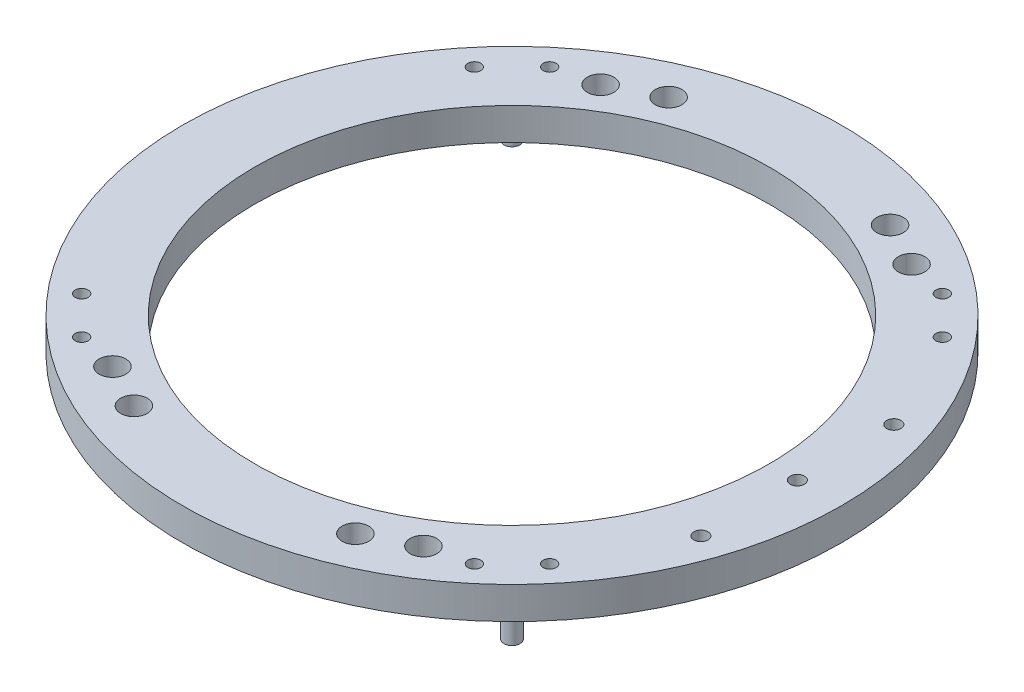
SolidWorks part; units mm, degrees
ref_plane "Front Plane" through (0, 0, 0) normal (0, 0, 1) x (1, 0, 0)
ref_plane "Top Plane" through (0, 0, 0) normal (0, 1, 0) x (1, 0, 0)
ref_plane "Right Plane" through (0, 0, 0) normal (1, 0, 0) x (0, 0, -1)
sketch "Sketch1" plane through (0, 0, 0) normal (0, 0, 1) x (1, 0, 0)
  line L0 (0, 1125.8152) -> (0, -48874.1848) construction
  line L1 (101.6, 1057.275) -> (114.3, 1057.275)
  line L3 (104.775, 955.675) -> (114.3, 955.675) construction
  line L4 (114.3, 1057.275) -> (114.3, 955.675) construction
  line L9 (101.6, 1069.975) -> (130.175, 1069.975)
  line L10 (101.6, 1069.975) -> (101.6, 1057.275)
  line L11 (101.6, 1057.275) -> (130.175, 1057.275)
  line L12 (130.175, 1069.975) -> (130.175, 1057.275)
  line L13 (104.775, 1057.275) -> (104.775, 955.675) construction
  line L14 (104.775, 1044.575) -> (104.775, 1057.275) construction
  line L15 (104.775, 968.375) -> (104.775, 955.675) construction
  line L16 (130.175, 955.675) -> (101.6, 955.675) construction
revolve "Revolve1" add sketch "Sketch1" angle 360 about L0 region at (115.8875, 1063.625, 0)
sketch "Sketch5" [suppressed] plane through (0, 1057.275, 0) normal (0, -1, 0) x (1, 0, 0)
  line L0 (0, 0) -> (107.3882, 47.625) construction
  line L1 (0, 0) -> (107.3882, -47.625) construction
  line L2 (0, 0) -> (117.475, 0) construction
  line L3 (107.3882, -47.625) -> (96.8765, -47.625)
  line L4 (107.3882, 47.625) -> (96.8765, 47.625)
  circle A0 centre (0, 0) radius 107.95 construction
  circle A1 centre (0, 0) radius 117.475
  arc A2 (107.3882, -47.625) -> (107.3882, 47.625) centre (0, 0) ccw
  circle A3 centre (0, 0) radius 107.95
  arc A4 (96.8765, -47.625) -> (96.8765, 47.625) centre (0, 0) ccw
  circle A5 centre (0, 0) radius 117.475 construction
  dimension "D3" = 95.25
  dimension "D1" = 0
  dimension "D2" = 0
extrude "Cut-Extrude1" [suppressed] cut sketch "Sketch5" along normal through all flip side to cut
sketch "Sketch11" [suppressed] plane through (0, 1057.275, 0) normal (0, -1, 0) x (1, 0, 0)
  line L0 (117.475, 47.625) -> (117.475, -47.625)
  line L1 (117.475, 47.625) -> (107.3882, 47.625)
  line L2 (107.3882, -47.625) -> (117.475, -47.625)
  arc A1 (107.3882, -47.625) -> (107.3882, 47.625) centre (0, 0) ccw construction
  arc A2 (107.3882, -47.625) -> (107.3882, 47.625) centre (0, 0) ccw
  point P3 (117.475, 0)
extrude "Boss-Extrude2" [suppressed] add sketch "Sketch11" along normal up to surface (101.6 mm away)
sketch "Sketch2" [suppressed] plane through (0, 0, 0) normal (0, 0, 1) x (1, 0, 0)
  line L0 (65.7096, 1044.575) -> (117.475, 1044.575)
  line L1 (117.475, 1044.575) -> (117.475, 1006.475)
  line L2 (184.3824, 1006.475) -> (0, 1006.475) construction
  line L3 (117.475, 1006.475) -> (65.7096, 1006.475)
  line L4 (65.7096, 1006.475) -> (65.7096, 1044.575)
  line L5 (184.3824, 1006.475) -> (0, 1006.475) construction
revolve "Cut-Revolve2" [suppressed] cut sketch "Sketch2" angle 360 about L5
sketch "Sketch6" plane through (0, 1057.275, 0) normal (0, -1, 0) x (1, 0, 0)
  line L0 (-85.3124, -85.3124) -> (85.3124, 85.3124) construction
  line L1 (-85.3124, 85.3124) -> (85.3124, -85.3124) construction
  line L2 (0, 0) -> (0, 120.65) construction
  circle A0 centre (0, 0) radius 120.65 construction
  circle A1 centre (-85.3124, 85.3124) radius 3.175
  circle A2 centre (85.3124, 85.3124) radius 3.175
  circle A3 centre (85.3124, -85.3124) radius 3.175
  circle A4 centre (-85.3124, -85.3124) radius 3.175
  point P5 (0, 0)
  point P8 (0, 0)
  dimension "D2" = 241.3
  dimension "D3" = 6.35
  dimension "D1" = 45
extrude "Boss-Extrude1" add sketch "Sketch6" along normal blind 12.7
hole_wizard "1/4-20 Tapped Hole1" positions "Sketch9" profile "Sketch10" tap size "1/4-20" standard "ANSI Inch" end condition through all
sketch "Sketch9" plane through (0, 1057.275, 0) normal (0, -1, 0) x (-1, 0, 0)
  line L0 (0, 0) -> (85.3124, 85.3124) construction
  line L3 (0, 0) -> (77.5523, 92.4233) construction
  arc A0 (77.5523, 92.4233) -> (92.4233, 77.5523) centre (0, 0) cw
  point P0 (77.5523, 92.4233)
  point P2 (92.4233, 77.5523)
  dimension "D1" = 5
sketch "Sketch10" plane through (-77.5523, 1057.275, -92.4233) normal (1, 0, 0) x (0, 0, -1)
  line L0 (0, 0) -> (0, 12.7)
  line L1 (0, 12.7) -> (2.5527, 12.7)
  line L2 (2.5527, 12.7) -> (2.5527, 0)
  line L5 (2.5527, 0) -> (0, 0)
  line L11 (0, -6.35) -> (0, 107.95) construction
  dimension "Thru Tap Drill Dia." = 5.1054
  dimension "Thru Tap Drill Depth" = 12.7
cosmetic thread "Hole Thread1" parameters "D2"=6.35
cosmetic thread "Hole Thread2" parameters "D2"=6.35
pattern_circular "CirPattern1" count 4 over 360 about axis through (0, 1125.8152, 0) along (0, 1, 0) of "1/4-20 Tapped Hole1"
ref_plane "Plane1" through (0, 1063.625, 0) normal (0, 1, 0) x (1, 0, 0)
sketch "Sketch12" plane through (0, 1063.625, 0) normal (0, 1, 0) x (1, 0, 0)
  line L0 (55.5625, -96.2371) -> (-55.5625, 96.2371) construction
  line L1 (55.5625, 96.2371) -> (-55.5625, -96.2371) construction
  line L2 (0, 0) -> (-111.125, 0) construction
  line L3 (-65.8243, -101.311) -> (-56.2993, -84.8132)
  line L4 (-65.8243, -101.311) -> (-54.8257, -107.661)
  line L5 (-56.2993, -84.8132) -> (-45.3007, -91.1632)
  line L6 (-54.8257, -107.661) -> (-45.3007, -91.1632)
  line L7 (-65.8243, -101.311) -> (-45.3007, -91.1632) construction
  line L8 (-56.2993, -84.8132) -> (-54.8257, -107.661) construction
  line L9 (-54.8257, 107.661) -> (-45.3007, 91.1632)
  line L10 (-54.8257, 107.661) -> (-65.8243, 101.311)
  line L11 (-45.3007, 91.1632) -> (-56.2993, 84.8132)
  line L12 (-65.8243, 101.311) -> (-56.2993, 84.8132)
  line L13 (-54.8257, 107.661) -> (-56.2993, 84.8132) construction
  line L14 (-45.3007, 91.1632) -> (-65.8243, 101.311) construction
  line L15 (0, 0) -> (0, 130.175) construction
  line L16 (45.3007, 91.1632) -> (65.8243, 101.311) construction
  line L17 (54.8257, 107.661) -> (56.2993, 84.8132) construction
  line L18 (56.2993, -84.8132) -> (54.8257, -107.661) construction
  line L19 (65.8243, -101.311) -> (45.3007, -91.1632) construction
  line L20 (65.8243, 101.311) -> (56.2993, 84.8132)
  line L21 (45.3007, 91.1632) -> (56.2993, 84.8132)
  line L22 (54.8257, 107.661) -> (65.8243, 101.311)
  line L23 (54.8257, 107.661) -> (45.3007, 91.1632)
  line L24 (54.8257, -107.661) -> (45.3007, -91.1632)
  line L25 (56.2993, -84.8132) -> (45.3007, -91.1632)
  line L26 (65.8243, -101.311) -> (54.8257, -107.661)
  line L27 (65.8243, -101.311) -> (56.2993, -84.8132)
  circle A0 centre (0, 0) radius 111.125 construction
  circle A1 centre (0, 0) radius 130.175 construction
  circle A3 centre (0, 0) radius 101.6 construction
  point P6 (0, 0)
  point P8 (0, 0)
  dimension "D1" = 60
  dimension "D3" = 19.05
  dimension "D4" = 12.7
extrude "Boss-Extrude3" [suppressed] add sketch "Sketch12" along normal mid plane 76.2
fillet "Fillet1" [suppressed] type full round
chamfer "Chamfer1" [suppressed] distance 15.875 angle 32.5
fillet "Fillet2" [suppressed] radius 6.35
fillet "Fillet3" [suppressed] radius 12.7
hole_wizard "#10 Clearance Hole1" positions "Sketch14" profile "Sketch15" hole size "#10" standard "ANSI Inch" end condition through all
sketch "Sketch14" plane through (0, 1069.975, 0) normal (0, 1, 0) x (1, 0, 0)
  point P0 (112.7125, 38.1)
  point P3 (112.7125, 0)
  point P6 (112.7125, -38.1)
sketch "Sketch15" plane through (112.7125, 1069.975, -38.1) normal (1, 0, 0) x (0, 0, 1)
  line L0 (0, 0) -> (0, 25.4)
  line L1 (0, 25.4) -> (2.8067, 25.4)
  line L2 (2.8067, 25.4) -> (2.8067, 0)
  line L5 (2.8067, 0) -> (0, 0)
  line L11 (0, -6.35) -> (0, 107.95) construction
  dimension "Thru Hole Dia." = 5.6134
  dimension "Thru Hole Depth" = 25.4
hole_wizard "Z (0.413) Diameter Hole1" positions "Sketch16" profile "Sketch17" hole size "Z" standard "ANSI Inch" end condition through all
sketch "Sketch16" plane through (0, 1069.975, 0) normal (0, 1, 0) x (1, 0, 0)
  line L0 (-43.7407, -105.5994) -> (43.7407, 105.5994) construction
  line L4 (43.7407, -105.5994) -> (-43.7407, 105.5994) construction
  line L6 (0, 0) -> (0, 114.3) construction
  line L8 (-61.4133, -96.3996) -> (61.4133, 96.3996) construction
  line L11 (-61.4133, 96.3996) -> (61.4133, -96.3996) construction
  circle A0 centre (0, 0) radius 114.3 construction
  point P0 (-43.7407, -105.5994)
  point P2 (43.7407, -105.5994)
  point P4 (43.7407, 105.5994)
  point P6 (-43.7407, 105.5994)
  point P37 (-61.4133, 96.3996)
  point P39 (61.4133, 96.3996)
  point P41 (61.4133, -96.3996)
  point P43 (-61.4133, -96.3996)
  dimension "D2" = 228.6
  dimension "D1" = 45
  dimension "D3" = 65
sketch "Sketch17" plane through (-43.7407, 1069.975, 105.5994) normal (1, 0, 0) x (0, 0, 1)
  line L0 (0, 0) -> (0, 25.4)
  line L1 (0, 25.4) -> (5.2451, 25.4)
  line L2 (5.2451, 25.4) -> (5.2451, 0)
  line L5 (5.2451, 0) -> (0, 0)
  line L11 (0, -6.35) -> (0, 107.95) construction
  dimension "Thru Hole Dia." = 10.4902
  dimension "Thru Hole Depth" = 25.4
